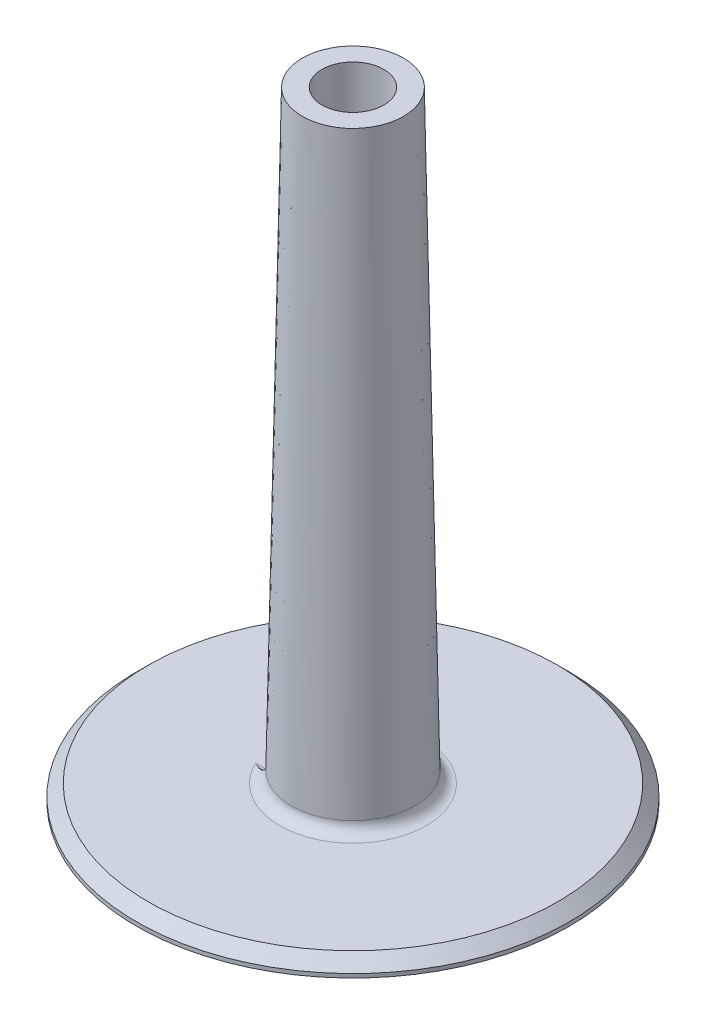
SolidWorks part; units mm, degrees
ref_plane "Front Plane" through (0, 0, 0) normal (0, 0, 1) x (1, 0, 0)
ref_plane "Top Plane" through (0, 0, 0) normal (0, 1, 0) x (1, 0, 0)
ref_plane "Right Plane" through (0, 0, 0) normal (1, 0, 0) x (0, 0, -1)
sketch "Sketch1" plane through (0, 0, 0) normal (1, 0, 0) x (0, 0, -1)
  line L0 (0, 254) -> (0, 0)
  line L1 (0, 0) -> (-12.7, 0)
  line L2 (-12.7, 0) -> (-7.9375, 254)
  line L3 (-7.9375, 254) -> (0, 254)
  dimension "D1" = 254
  dimension "D2" = 12.7
  dimension "D3" = 7.9375
revolve "Revolve1" add sketch "Sketch1" angle 360 about L0
sketch "Sketch3" plane through (0, 254, 0) normal (0, 1, 0) x (1, 0, 0)
  circle A0 centre (0, 0) radius 6.35
  dimension "D1" = 12.7
extrude "Cut-Extrude1" cut sketch "Sketch3" against normal through all
sketch "Sketch4" plane through (0, 0, 0) normal (0, -1, 0) x (1, 0, 0)
  circle A0 centre (0, 0) radius 44.45
  dimension "D1" = 88.9
extrude "Boss-Extrude1" add sketch "Sketch4" along normal blind 3.175
chamfer "Chamfer1" distance 2.38 angle 45 1 edges at (0, 0, -44.45)
sketch "Sketch6" plane through (0, 254, 0) normal (0, 1, 0) x (1, 0, 0)
  circle A0 centre (0, 0) radius 7.9375
  circle A1 centre (0, 0) radius 6.35
  circle A2 centre (0, 0) radius 6.35 construction
  circle A3 centre (0, 0) radius 7.9375 construction
extrude "Boss-Extrude3" add sketch "Sketch6" along normal blind 6.35
sketch "Sketch7" plane through (0, 0, 0) normal (1, 0, 0) x (0, 0, -1)
  line L0 (-6.35, 1.524) -> (6.35, 1.524) construction
  line L1 (-6.35, 3.048) -> (6.35, 3.048)
  line L2 (-6.35, 0) -> (6.35, 0)
  line L3 (42.07, 0) -> (-42.07, 0) construction
  arc A0 (-6.35, 3.048) -> (-6.35, 0) centre (-6.35, 1.524) ccw
  arc A1 (6.35, 0) -> (6.35, 3.048) centre (6.35, 1.524) ccw
  point P2 (0, 1.524)
  dimension "D1" = 12.7
  dimension "D2" = 1.524
extrude "Cut-Extrude2" cut sketch "Sketch7" against normal blind 16.51
fillet "Fillet1" radius 2.38 1 edges at (12.7, 0, 0)
sketch "Sketch8" plane through (0, 0, 0) normal (0, 0, 1) x (1, 0, 0)
  line L0 (-44.45, -3.175) -> (44.45, -3.175) construction
  line L1 (-53.2005, 263.6385) -> (55.4712, 263.6385)
  line L2 (-53.2005, 263.6385) -> (-53.2005, 123.825)
  line L3 (-53.2005, 123.825) -> (55.4712, 123.825)
  line L4 (55.4712, 263.6385) -> (55.4712, 123.825)
  dimension "D1" = 127
extrude "Cut-Extrude3" cut sketch "Sketch8" against normal mid plane 76.2
